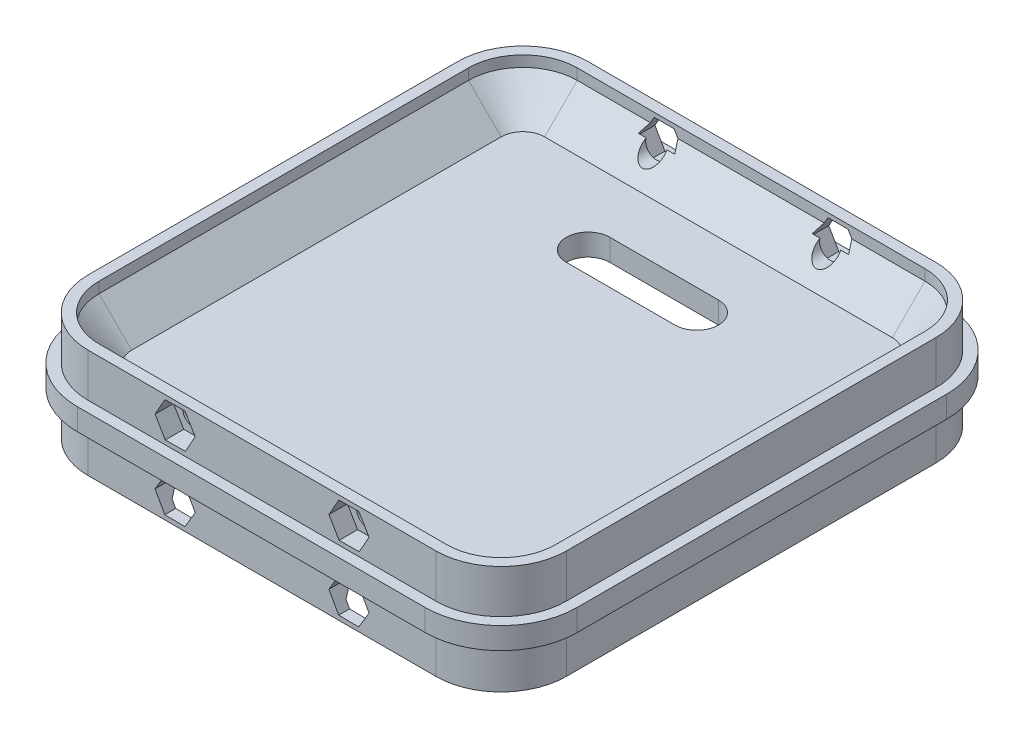
SolidWorks part; units mm, degrees
ref_plane "Front Plane" through (0, 0, 0) normal (0, 0, 1) x (1, 0, 0)
ref_plane "Top Plane" through (0, 0, 0) normal (0, 1, 0) x (1, 0, 0)
ref_plane "Right Plane" through (0, 0, 0) normal (1, 0, 0) x (0, 0, -1)
sketch "Sketch1" plane through (0, 0, 0) normal (0, 1, 0) x (1, 0, 0)
  line L0 (713.4525, 539.6819) -> (1957.9026, 539.6819) construction
  line L1 (-5, 30) -> (-5, 200)
  line L2 (30, 0) -> (190, 0)
  line L3 (0, 30) -> (0, 200)
  line L4 (30, 230) -> (190, 230)
  line L5 (220, 30) -> (220, 200)
  line L6 (30, 235) -> (190, 235)
  line L7 (225, 30) -> (225, 200)
  line L8 (30, -5) -> (190, -5)
  arc A0 (30, 230) -> (0, 200) centre (30, 200) ccw
  arc A1 (190, 230) -> (220, 200) centre (190, 200) cw
  arc A2 (220, 30) -> (190, 0) centre (190, 30) cw
  arc A3 (0, 30) -> (30, 0) centre (30, 30) ccw
  arc A4 (30, 235) -> (-5, 200) centre (30, 200) ccw
  arc A5 (190, 235) -> (225, 200) centre (190, 200) cw
  arc A6 (225, 30) -> (190, -5) centre (190, 30) cw
  arc A7 (-5, 30) -> (30, -5) centre (30, 30) ccw
  point P13 (220, 0)
  point P16 (0, 0)
  dimension "D3" = 30
  dimension "D1" = 230
  dimension "D2" = 220
  dimension "D4" = 5
extrude "Boss-Extrude1" add sketch "Sketch1" along normal blind 30 and the other way blind 20 contours L5 A1 L4 A0 L3 A3 L2 A2
extrude "Boss-Extrude2" add sketch "Sketch1<3>" along normal blind 10
sketch "Sketch1<3>" plane through (0, 0, 0) normal (0, 1, 0) x (1, 0, 0) same geometry as "Sketch1"
sketch "Sketch2" plane through (0, 0, -230) normal (0, 0, -1) x (-1, 0, 0)
  line L2 (-190, 20) -> (-30, 20) construction
  line L3 (-190, 10) -> (-190, 30) construction
  line L4 (-30, 10) -> (-30, 30) construction
  line L5 (-190, 10) -> (-30, 10) construction
  line L6 (-110, 30) -> (-110, 10) construction
  line L7 (-30, 30) -> (-190, 30) construction
  line L8 (-74.6188, 12) -> (-79.2376, 20)
  line L9 (-140.7624, 20) -> (-145.3812, 28)
  line L10 (-145.3812, 28) -> (-154.6188, 28)
  line L11 (-154.6188, 28) -> (-159.2376, 20)
  line L12 (-159.2376, 20) -> (-154.6188, 12)
  line L13 (-154.6188, 12) -> (-145.3812, 12)
  line L14 (-145.3812, 12) -> (-140.7624, 20)
  line L15 (-65.3812, 12) -> (-74.6188, 12)
  line L16 (-60.7624, 20) -> (-65.3812, 12)
  line L17 (-65.3812, 28) -> (-60.7624, 20)
  line L18 (-74.6188, 28) -> (-65.3812, 28)
  line L19 (-79.2376, 20) -> (-74.6188, 28)
  line L20 (-110, 30) -> (-110, -20) construction
  line L21 (-30, -20) -> (-190, -20) construction
  line L22 (-110, 5) -> (-201.1857, 5) construction
  line L23 (-201.1857, 5) -> (-28.2412, 5) construction
  line L24 (-65.3812, -2) -> (-74.6188, -2)
  line L25 (-60.7624, -10) -> (-65.3812, -2)
  line L26 (-65.3812, -18) -> (-60.7624, -10)
  line L27 (-74.6188, -18) -> (-65.3812, -18)
  line L28 (-79.2376, -10) -> (-74.6188, -18)
  line L29 (-74.6188, -2) -> (-79.2376, -10)
  line L30 (-145.3812, -2) -> (-140.7624, -10)
  line L31 (-154.6188, -2) -> (-145.3812, -2)
  line L32 (-159.2376, -10) -> (-154.6188, -2)
  line L33 (-154.6188, -18) -> (-159.2376, -10)
  line L34 (-145.3812, -18) -> (-154.6188, -18)
  line L35 (-140.7624, -10) -> (-145.3812, -18)
  circle A0 centre (-150, 20) radius 5
  circle A1 centre (-150, 20) radius 8 construction
  circle A2 centre (-70, 20) radius 5
  circle A3 centre (-70, 20) radius 8 construction
  circle A4 centre (-70, -10) radius 8 construction
  circle A5 centre (-70, -10) radius 5
  circle A6 centre (-150, -10) radius 8 construction
  circle A7 centre (-150, -10) radius 5
  point P14 (-70, 20)
  point P45 (-70, -10)
  point P47 (-150, -10)
  dimension "D2" = 10
  dimension "D3" = 16
  dimension "D1" = 10
  dimension "D4" = 40
sketch "Sketch3" plane through (0, 0, 0) normal (0, 0, 1) x (1, 0, 0)
  line L1 (58.0861, 17.2863) -> (66.3932, 8.3254)
  line L2 (66.3932, 8.3254) -> (78.3071, 11.0391)
  line L3 (78.3071, 11.0391) -> (81.9139, 22.7137)
  line L4 (81.9139, 22.7137) -> (73.6068, 31.6746)
  line L5 (73.6068, 31.6746) -> (61.6929, 28.9609)
  line L6 (61.6929, 28.9609) -> (58.0861, 17.2863)
  line L7 (138.0861, 17.2863) -> (146.3932, 8.3254)
  line L8 (146.3932, 8.3254) -> (158.3071, 11.0391)
  line L9 (158.3071, 11.0391) -> (161.9139, 22.7137)
  line L10 (161.9139, 22.7137) -> (153.6068, 31.6746)
  line L11 (153.6068, 31.6746) -> (141.6929, 28.9609)
  line L12 (141.6929, 28.9609) -> (138.0861, 17.2863)
  line L13 (137.1029, -11.4747) -> (144.8286, -21.9066)
  line L14 (144.8286, -21.9066) -> (157.7257, -20.4319)
  line L15 (157.7257, -20.4319) -> (162.8971, -8.5253)
  line L16 (162.8971, -8.5253) -> (155.1714, 1.9066)
  line L17 (155.1714, 1.9066) -> (142.2743, 0.4319)
  line L18 (142.2743, 0.4319) -> (137.1029, -11.4747)
  line L19 (57.1029, -11.4747) -> (64.8286, -21.9066)
  line L20 (64.8286, -21.9066) -> (77.7257, -20.4319)
  line L21 (77.7257, -20.4319) -> (82.8971, -8.5253)
  line L22 (82.8971, -8.5253) -> (75.1714, 1.9066)
  line L23 (75.1714, 1.9066) -> (62.2743, 0.4319)
  line L24 (62.2743, 0.4319) -> (57.1029, -11.4747)
  circle A0 centre (70, 20) radius 5
  circle A1 centre (150, 20) radius 5
  circle A2 centre (150, -10) radius 5
  circle A3 centre (70, -10) radius 5
  circle A4 centre (70, 20) radius 10.582 construction
  circle A5 centre (150, 20) radius 10.582 construction
  circle A6 centre (150, -10) radius 11.242 construction
  circle A7 centre (70, -10) radius 11.242 construction
extrude "Cut-Extrude1" cut sketch "Sketch2" against normal blind 30 contours A0 | A2 | A5 | A7
extrude "Cut-Extrude3" cut sketch "Sketch3" against normal blind 30 contours A0 | A1 | A2 | A3
sketch "Sketch4" plane through (0, 30, 0) normal (0, 1, 0) x (1, 0, 0)
  line L0 (110, 230) -> (110, 0) construction
  line L1 (30, 230) -> (190, 230) construction
  line L2 (30, 0) -> (190, 0) construction
  line L3 (220, 115) -> (0, 115) construction
  line L4 (220, 30) -> (220, 200) construction
  line L5 (0, 30) -> (0, 200) construction
  line L6 (0, 175) -> (220, 175) construction
  line L7 (135, 175) -> (85, 175) construction
  line L8 (135, 165) -> (85, 165)
  line L9 (135, 185) -> (85, 185)
  arc A0 (135, 165) -> (135, 185) centre (135, 175) ccw
  arc A1 (85, 185) -> (85, 165) centre (85, 175) ccw
  point P16 (110, 175)
  dimension "D2" = 10
  dimension "D1" = 60
  dimension "D3" = 50
extrude "Cut-Extrude5" cut sketch "Sketch4" against normal through all
sketch "Sketch7" plane through (0, 30, 0) normal (0, 1, 0) x (1, 0, 0)
  line L8 (215, 30) -> (215, 200)
  line L9 (190, 225) -> (30, 225)
  line L10 (5, 200) -> (5, 30)
  line L11 (30, 5) -> (190, 5)
  line L12 (215, 30) -> (215, 200)
  line L13 (190, 225) -> (30, 225)
  line L14 (5, 200) -> (5, 30)
  line L15 (30, 5) -> (190, 5)
  arc A8 (190, 5) -> (215, 30) centre (190, 30) ccw
  arc A9 (215, 200) -> (190, 225) centre (190, 200) ccw
  arc A10 (30, 225) -> (5, 200) centre (30, 200) ccw
  arc A11 (5, 30) -> (30, 5) centre (30, 30) ccw
  arc A12 (190, 5) -> (215, 30) centre (190, 30) ccw
  arc A13 (215, 200) -> (190, 225) centre (190, 200) ccw
  arc A14 (30, 225) -> (5, 200) centre (30, 200) ccw
  arc A15 (5, 30) -> (30, 5) centre (30, 30) ccw
  dimension "D1" = 5
extrude "Cut-Extrude7" cut sketch "Sketch7" against normal blind 20
sketch "Sketch9" plane through (0, -20, 0) normal (0, -1, 0) x (1, 0, 0)
  line L8 (190, -5) -> (30, -5)
  line L9 (5, -30) -> (5, -200)
  line L10 (30, -225) -> (190, -225)
  line L11 (215, -200) -> (215, -30)
  line L12 (190, -5) -> (30, -5)
  line L13 (5, -30) -> (5, -200)
  line L14 (30, -225) -> (190, -225)
  line L15 (215, -200) -> (215, -30)
  arc A8 (215, -30) -> (190, -5) centre (190, -30) ccw
  arc A9 (30, -5) -> (5, -30) centre (30, -30) ccw
  arc A10 (5, -200) -> (30, -225) centre (30, -200) ccw
  arc A11 (190, -225) -> (215, -200) centre (190, -200) ccw
  arc A12 (215, -30) -> (190, -5) centre (190, -30) ccw
  arc A13 (30, -5) -> (5, -30) centre (30, -30) ccw
  arc A14 (5, -200) -> (30, -225) centre (30, -200) ccw
  arc A15 (190, -225) -> (215, -200) centre (190, -200) ccw
  dimension "D1" = 5
extrude "Cut-Extrude8" cut sketch "Sketch9" against normal blind 20
chamfer "Chamfer7" distance 15 angle 45 16 edges at (110, 10, -5) (12.3223, 10, -217.6777) (12.3223, 10, -12.3223) (5, 10, -115) (207.6777, 10, -12.3223) (207.6777, 10, -217.6777) (215, 10, -115) (110, 10, -225) (5, 0, -115) (12.3223, 0, -217.6777) (12.3223, 0, -12.3223) (110, 0, -225) (110, 0, -5) (207.6777, 0, -217.6777) (207.6777, 0, -12.3223) (215, 0, -115)
sketch "Sketch6" plane through (0, 0, 0) normal (0, 0, 1) x (1, 0, 0)
  line L1 (140.7628, 19.9101) -> (145.4593, 11.9554)
  line L2 (65.2851, 27.9437) -> (60.7631, 19.8887)
  line L3 (60.7631, 19.8887) -> (65.478, 11.9449)
  line L4 (65.478, 11.9449) -> (74.7149, 12.0563)
  line L5 (74.7149, 12.0563) -> (79.2369, 20.1113)
  line L6 (79.2369, 20.1113) -> (74.522, 28.0551)
  line L7 (74.522, 28.0551) -> (65.2851, 27.9437)
  line L8 (145.4593, 11.9554) -> (154.6965, 12.0453)
  line L9 (154.6965, 12.0453) -> (159.2372, 20.0899)
  line L10 (159.2372, 20.0899) -> (154.5407, 28.0446)
  line L11 (154.5407, 28.0446) -> (145.3035, 27.9547)
  line L12 (145.3035, 27.9547) -> (140.7628, 19.9101)
  line L13 (140.7633, -9.8697) -> (145.2688, -17.9341)
  line L14 (145.2688, -17.9341) -> (154.5055, -18.0643)
  line L15 (154.5055, -18.0643) -> (159.2367, -10.1303)
  line L16 (159.2367, -10.1303) -> (154.7312, -2.0659)
  line L17 (154.7312, -2.0659) -> (145.4945, -1.9357)
  line L18 (145.4945, -1.9357) -> (140.7633, -9.8697)
  line L19 (60.7633, -9.8697) -> (65.2688, -17.9341)
  line L20 (65.2688, -17.9341) -> (74.5055, -18.0643)
  line L21 (74.5055, -18.0643) -> (79.2367, -10.1303)
  line L22 (79.2367, -10.1303) -> (74.7312, -2.0659)
  line L23 (74.7312, -2.0659) -> (65.4945, -1.9357)
  line L24 (65.4945, -1.9357) -> (60.7633, -9.8697)
  circle A0 centre (70, 20) radius 8 construction
  circle A1 centre (150, 20) radius 8 construction
  circle A2 centre (150, -10) radius 8 construction
  circle A3 centre (70, -10) radius 8 construction
  dimension "D1" = 16
  dimension "D2" = 16
  dimension "D3" = 16
  dimension "D4" = 16
extrude "Cut-Extrude6" cut sketch "Sketch6" against normal blind 8.5
extrude "Cut-Extrude2" cut sketch "Sketch2<4>" against normal blind 8.5
sketch "Sketch2<4>" plane through (0, 0, -230) normal (0, 0, -1) x (-1, 0, 0) same geometry as "Sketch2"
